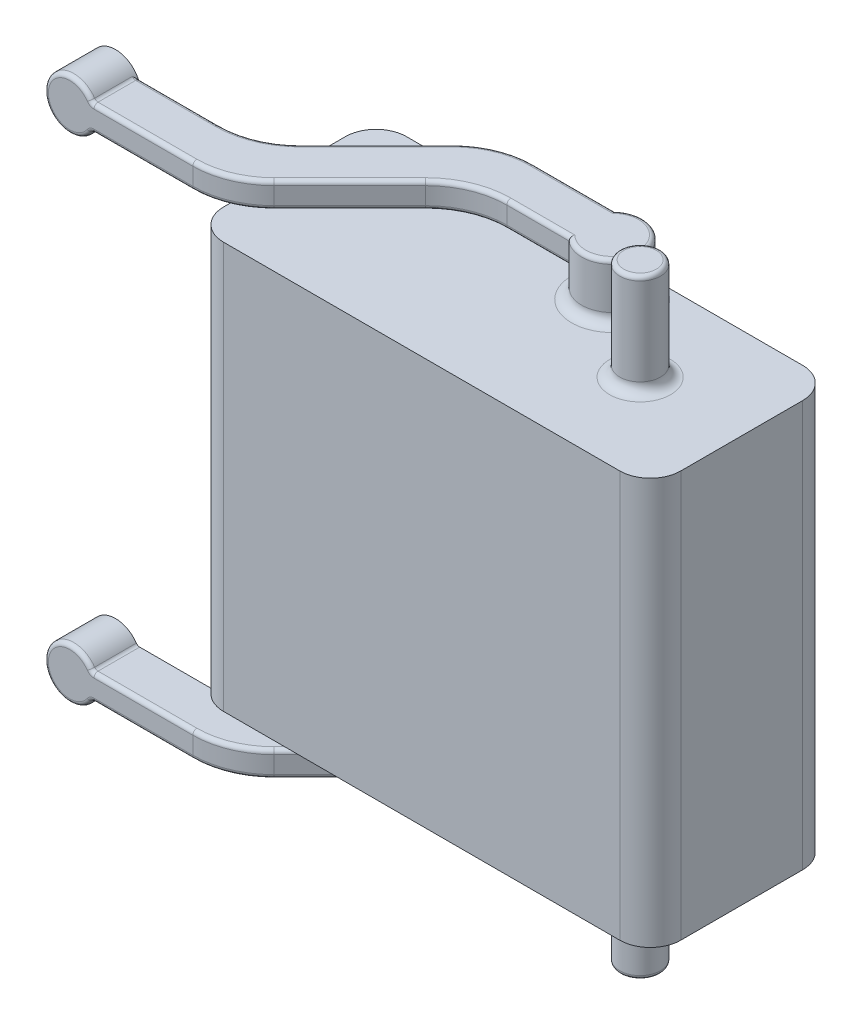
SolidWorks part; units mm, degrees
ref_plane "Front Plane" through (0, 0, 0) normal (0, 0, 1) x (1, 0, 0)
ref_plane "Top Plane" through (0, 0, 0) normal (0, 1, 0) x (1, 0, 0)
ref_plane "Right Plane" through (0, 0, 0) normal (1, 0, 0) x (0, 0, -1)
sketch "Sketch1" plane through (0, 0, 0) normal (0, 1, 0) x (1, 0, 0)
  circle A0 centre (0, 0) radius 20
  dimension "D1" = 40
extrude "Boss-Extrude1" add sketch "Sketch1" along normal blind 300
sketch "Sketch2" plane through (0, 0, 0) normal (1, 0, 0) x (0, 0, -1)
  line L1 (-90, 0) -> (90, 0)
  line L2 (-90, 0) -> (-90, 200)
  line L3 (-90, 200) -> (90, 200)
  line L4 (90, 0) -> (90, 200)
  dimension "D1" = 180
  dimension "D2" = 90
  dimension "D3" = 200
extrude "Boss-Extrude2" add sketch "Sketch2" along normal blind 100 and the other way blind 350
ref_plane "Plane1" through (0, 230, 0) normal (0, 1, 0) x (1, 0, 0)
sketch "Sketch4" plane through (0, 230, 0) normal (0, 1, 0) x (1, 0, 0)
  line L0 (-80, 30) -> (-194.3237, 30)
  line L1 (-194.3237, 30) -> (-315.7237, -91.4)
  line L2 (-315.7237, -91.4) -> (-470, -91.4)
  line L3 (-470, -91.4) -> (-470, -46.4)
  line L4 (-470, -46.4) -> (-334.3633, -46.4)
  line L5 (-334.3633, -46.4) -> (-212.9633, 75)
  line L6 (-212.9633, 75) -> (-80, 75)
  line L7 (-80, 75) -> (-80, 30)
  line L8 (-350, 90) -> (-350, -90) construction
  circle A0 centre (0, 0) radius 20 construction
  dimension "D1" = 45
  dimension "D2" = 45
  dimension "D3" = 45
  dimension "D4" = 30
  dimension "D5" = 135
  dimension "D6" = 114.3237
  dimension "D7" = 80
  dimension "D8" = 120
  dimension "D9" = 76.4
extrude "Boss-Extrude3" add sketch "Sketch4" along normal blind 25 separate body
sketch "Sketch5" plane through (0, 200, 0) normal (0, 1, 0) x (1, 0, 0)
  line L0 (-80, 30) -> (-80, 75) construction
  circle A0 centre (-80, 52.5) radius 30
  dimension "D1" = 60
extrude "Boss-Extrude4" add sketch "Sketch5" along normal up to surface (55 mm away) up to face at (-269.6718, 255, 8.2)
sketch "Sketch6" plane through (0, 0, 91.4) normal (0, 0, 1) x (1, 0, 0)
  line L0 (-470, 255) -> (-470, 230) construction
  circle A0 centre (-470, 242.5) radius 25
  dimension "D1" = 50
extrude "Boss-Extrude5" add sketch "Sketch6" against normal blind 50
sketch "Sketch7" plane through (0, 0, 41.4) normal (0, 0, -1) x (-1, 0, 0)
  circle A0 centre (470, 242.5) radius 15
  dimension "D1" = 30
extrude "Boss-Extrude6" add sketch "Sketch7" along normal blind 10
ref_plane "Plane2" through (0, 242.5, 0) normal (0, -1, 0) x (-1, 0, 0)
sketch "Sketch8" plane through (0, 242.5, 0) normal (0, -1, 0) x (-1, 0, 0)
  line L1 (455, -31.4) -> (485, -31.4)
  line L2 (455, -31.4) -> (455, -41.4)
  line L3 (455, -41.4) -> (485, -41.4)
  line L4 (485, -31.4) -> (485, -41.4)
extrude "Boss-Extrude7" add sketch "Sketch8" along normal blind 100
sketch "Sketch9" plane through (0, 0, 31.4) normal (0, 0, -1) x (-1, 0, 0)
  line L0 (485, 142.5) -> (485, 242.5) construction
  line L1 (455, 142.5) -> (485, 142.5)
  line L2 (455, 142.5) -> (455, 152.5)
  line L3 (455, 152.5) -> (485, 152.5)
  line L4 (485, 142.5) -> (485, 152.5)
  dimension "D1" = 10
extrude "Boss-Extrude8" add sketch "Sketch9" along normal blind 56.9
sketch "Sketch11" plane through (-485, 0, 0) normal (-1, 0, 0) x (0, 0, 1)
  line L0 (-25.5, 142.5) -> (-86.5715, 273.4682)
  line L1 (-86.5715, 273.4682) -> (-76.5715, 273.4682)
  line L2 (-76.5715, 273.4682) -> (-15.5, 142.5)
  line L3 (41.4, 142.5) -> (-25.5, 142.5) construction
  line L4 (-15.5, 142.5) -> (-25.5, 142.5)
  line L5 (-25.5, 152.5) -> (31.4, 152.5) construction
  dimension "D1" = 115
  dimension "D2" = 10
extrude "Boss-Extrude10" add sketch "Sketch11" against normal up to surface (30 mm away) up to face at (-455, 185.3571, 19.4286)
sketch "Sketch12" plane through (0, 0, 41.4) normal (0, 0, -1) x (-1, 0, 0)
  circle A0 centre (470, 242.5) radius 30
  dimension "D1" = 60
extrude "Boss-Extrude11" add sketch "Sketch12" along normal blind 10
sketch "Sketch13" plane through (0, 273.4682, 0) normal (0, 1, 0) x (1, 0, 0)
  line L1 (-455, 86.5715) -> (-455, 76.5715) construction
  circle A0 centre (-470, 85) radius 17.5
  dimension "D1" = 35
  dimension "D2" = 85
  dimension "D3" = 15
extrude "Boss-Extrude12" add sketch "Sketch13" along normal up to surface (26.5318 mm away) up to face at (0, 300, 20)
fillet "Fillet1" radius 80 4 edges at (-334.3633, 242.5, 46.4) (-212.9633, 242.5, -75) (-315.7237, 242.5, 91.4) (-194.3237, 242.5, -30)
fillet "Fillet2" radius 10 2 edges at (-80, 200, -22.5) (0, 200, 20)
fillet "Fillet3" radius 30 4 edges at (-470, 142.5, -25.5) (-470, 142.5, 41.4) (-470, 152.5, 31.4) (-470, 152.5, -20.1631)
fillet "Fillet4" radius 4 6 edges at (-470, 300, -67.5) (0, 300, 20) (-470, 273.4682, -67.5) (-448.3494, 255, 68.9) (-448.3494, 230, 68.9) (-445, 242.5, 41.4)
fillet "Fillet5" radius 4 20 edges at (-130.5149, 230, -30) (-191.8013, 230, -23.9104) (-255.0237, 230, 30.7) (-318.2461, 230, 85.3104) (-397.5062, 230, 91.4) (-448.0085, 229.5428, 91.4) (-495, 242.5, 91.4) (-448.0085, 255.4572, 91.4) (-448.0085, 255.4572, 46.4) (-336.8857, 255, 40.3104) (-273.6633, 255, -14.3) (-210.4409, 255, -68.9104) (-139.8347, 255, -75) (-50, 255, -52.5) (-130.5149, 255, -30) (-191.8013, 255, -23.9104) (-255.0237, 255, 30.7) (-318.2461, 255, 85.3104) (-397.5062, 255, 91.4) (-406.826, 255, 46.4)
fillet "Fillet8" radius 30 4 edges at (-350, 100, -90) (-350, 100, 90) (100, 100, -90) (100, 100, 90)
sketch "Sketch15" plane through (0, 0, 46.4) normal (0, 0, 1) x (1, 0, 0)
  line L1 (-532.7454, 320.2158) -> (-432.387, 320.2158)
  line L2 (-532.7454, 320.2158) -> (-532.7454, 74.8953)
  line L3 (-532.7454, 74.8953) -> (-432.387, 74.8953)
  line L4 (-432.387, 320.2158) -> (-432.387, 74.8953)
extrude "Cut-Extrude2" cut sketch "Sketch15" against normal blind 343
mirror "Mirror2" about plane through (0, 0, 0) normal (0, 1, 0) of bodies 114
equation "\"D2@Sketch2\"=\"D1@Sketch2\"/2"
equation "\"D2@Sketch4\"=\"D1@Sketch4\""
equation "\"D3@Sketch4\"=\"D1@Sketch4\""
